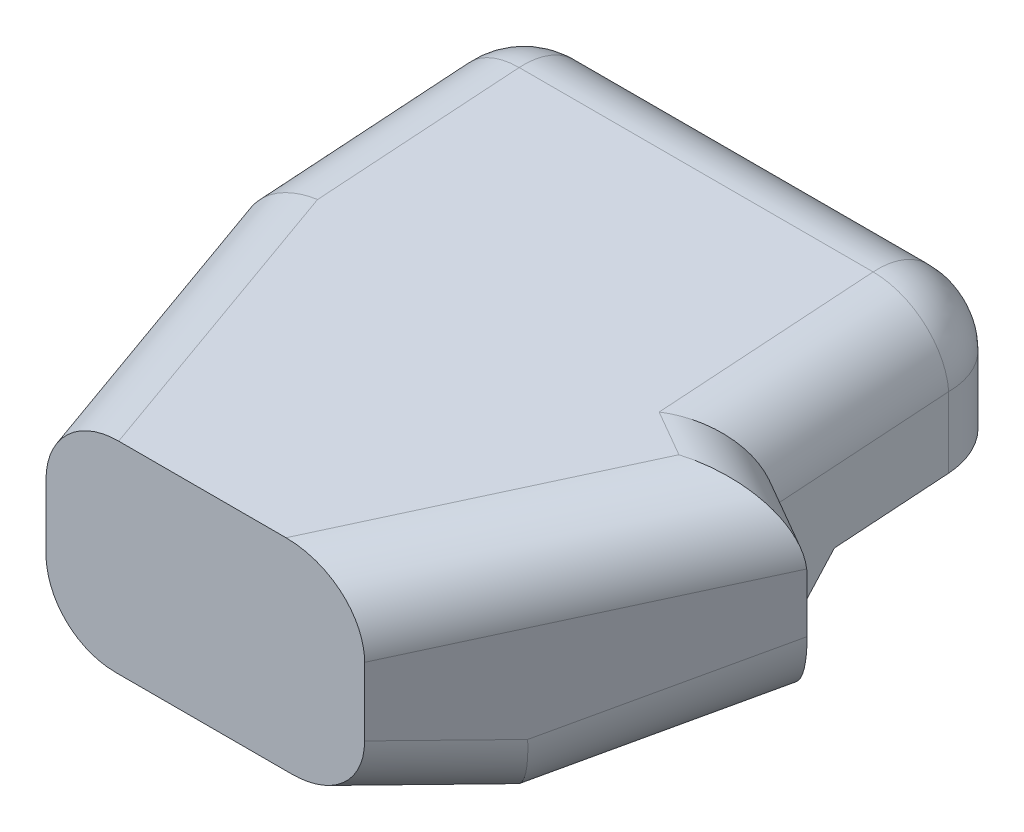
SolidWorks part; units mm, degrees
ref_plane "Front" through (0, 0, 0) normal (0, 0, 1) x (1, 0, 0)
ref_plane "Top" through (0, 0, 0) normal (0, 1, 0) x (1, 0, 0)
ref_plane "Right" through (0, 0, 0) normal (1, 0, 0) x (0, 0, -1)
sketch "Sketch1" plane through (0, 0, 0) normal (0, 1, 0) x (1, 0, 0)
  line L0 (-44.45, 101.6) -> (44.45, 101.6)
  line L2 (57.15, 50.8) -> (28.575, 0)
  line L3 (28.575, 0) -> (-28.575, 0)
  line L4 (-28.575, 0) -> (-44.45, 50.8)
  line L6 (-44.45, 50.8) -> (-44.45, 101.6)
  line L7 (0, 0) -> (0, 101.6) construction
  line L8 (57.15, 50.8) -> (44.45, 57.9437)
  line L9 (44.45, 57.9437) -> (44.45, 101.6)
  dimension "D1" = 88.9
  dimension "D2" = 57.15
  dimension "D3" = 101.6
  dimension "D4" = 50.8
  dimension "D5" = 12.7
extrude "Extrude1" add sketch "Sketch1" along normal blind 48.26
ref_axis "Axis1" through (0, 0, 22.3254) along (0, 0, -1)
sketch "Sketch3" plane through (-44.45, 0, 0) normal (-1, 0, 0) x (0, 0, 1)
  line L0 (0, 41.4453) -> (-101.6, 48.26)
  line L1 (0, 48.26) -> (0, 0) construction
  line L2 (0, 5.2406) -> (-25.4, 0)
  line L3 (-50.8, 0) -> (0, 0) construction
  line L4 (-25.4, 0) -> (-57.9437, 9.0846)
  line L6 (-57.9437, 9.0846) -> (-68.3976, 20.633)
  line L7 (-68.3976, 20.633) -> (-101.6, 22.86)
  line L9 (-57.9437, 48.26) -> (-57.9437, 0) construction
  line L10 (0, 5.2406) -> (0, 41.4453)
  line L11 (-101.6, 48.26) -> (-101.6, 22.86)
  dimension "D1" = 25.4
extrude "Cut-Extrude1" cut sketch "Sketch3" against normal mid plane 254 flip side to cut
sketch "Sketch4" plane through (24.2408, 0, -69.3114) normal (-0.4903, 0, 0.8716) x (0.8716, 0, 0.4903)
  line L0 (37.7583, 0) -> (-31.423, 0) construction
  line L2 (23.187, 45.3318) -> (37.7583, 7.0904) construction
  point P0 (30.4727, 26.2111)
sketch "Sketch5" plane through (20.8472, -1.8972, -101.6) normal (0, 0, -1) x (-1, 0, 0)
  line L0 (-23.6028, 37.4572) -> (65.2972, 37.4572) construction
  line L1 (-23.6028, 50.1572) -> (-23.6028, 24.7572) construction
  line L4 (65.2972, 50.1572) -> (65.2972, 24.7572) construction
  point P0 (-10.2057, 37.4572)
  point P1 (11.0496, 37.4572)
  point P2 (31.9024, 37.4572)
  point P3 (53.5765, 37.4572)
sketch "Sketch7" plane through (0, 0, 0) normal (0, 0, 1) x (1, 0, 0)
  line L0 (-28.575, 41.4453) -> (28.575, 5.2406) construction
  line L1 (-28.575, 5.2406) -> (28.575, 41.4453) construction
  point P0 (0, 23.3429)
fillet "Fillet1" radius 12.7 8 edges at (-44.45, 35.56, -101.6) (-44.45, 46.5563, -76.2) (42.8625, 43.149, -25.4) (0, 48.26, -101.6) (50.8, 45.0922, -54.3719) (44.45, 35.56, -101.6) (44.45, 46.7959, -79.7719) (-36.5125, 43.149, -25.4)
fillet "Fillet2" radius 12.7 4 edges at (-40.4813, 3.5452, -38.1) (-32.5438, 2.6203, -12.7) (50.0062, 3.5452, -38.1) (35.7187, 2.6203, -12.7)
